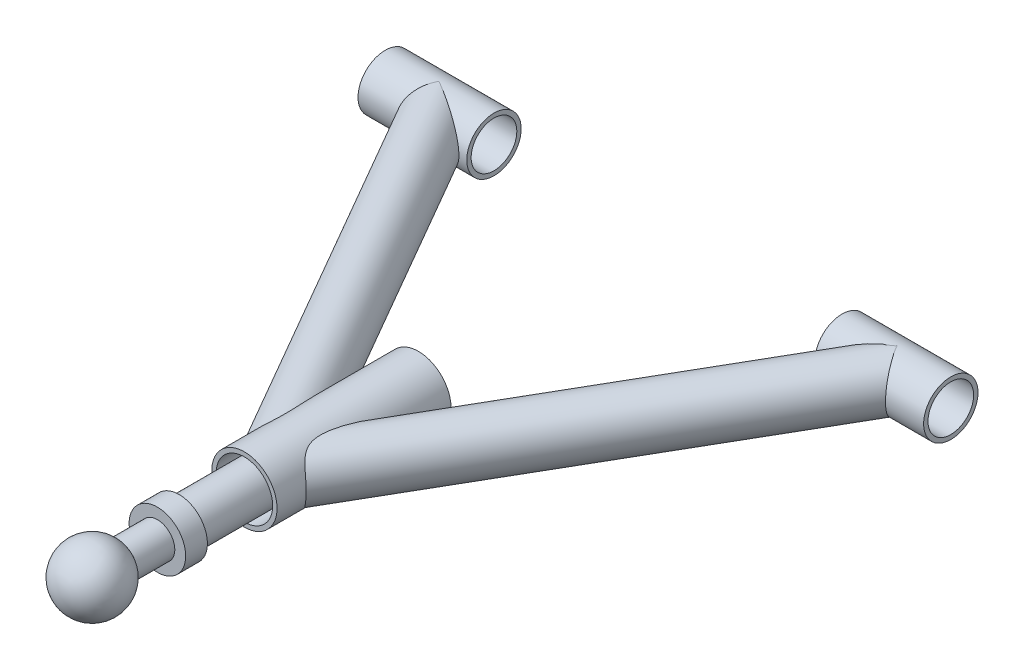
SolidWorks part; units mm, degrees
note: '?' marks a value the reader was unsure of.
ref_plane "前视基准面" through (0, 0, 0) normal (0, 0, 1) x (1, 0, 0)
ref_plane "上视基准面" through (0, 0, 0) normal (0, 1, 0) x (1, 0, 0)
ref_plane "右视基准面" through (0, 0, 0) normal (1, 0, 0) x (0, 0, -1)
sketch "草图1" plane through (0, 0, 0) normal (0, 0, 1) x (1, 0, 0)
  circle A0 centre (0, 0) radius 13
  circle A1 centre (0, 0) radius 15
  dimension "D1" = 30
  dimension "D2" = 2
extrude "凸台-拉伸1" add sketch "草图1" along normal blind 80
ref_axis "基准轴1" through (0, 13.75, 0) along (0, -1, 0)?
ref_plane "基准面1" through (0, 0, 0) normal (-0.5, 0, 0.866) x (0, -1, 0)
ref_plane "基准面2" through (0, 0, 0) normal (0.5, 0, 0.866) x (0, -1, 0)
sketch "草图3" plane through (0, 0, 0) normal (1, 0, 0) x (0, 0, -1)
  circle A0 centre (114.7344, 0) radius 12.5
  circle A1 centre (114.7344, 0) radius 10.5
  dimension "D2" = 25
  dimension "D1" = 2
extrude "凸台-拉伸3" add sketch "草图3" along normal blind 50 from offset 80 separate body
sketch "草图2" plane through (0, 0, 0) normal (-0.5, 0, 0.866) x (0, -1, 0)
  circle A0 centre (0, 33.8007) radius 12.5
  circle A1 centre (0, 33.8007) radius 10.5
  dimension "D1" = 25
  dimension "D2" = 2
extrude "凸台-拉伸2" add sketch "草图2" along normal up to next and the other way up to next
mirror "镜向14" about plane through (0, 0, 0) normal (1, 0, 0) of "凸台-拉伸1", "凸台-拉伸3", "凸台-拉伸2"
sketch "草图4" plane through (0, 0, 0) normal (0, 1, 0) x (1, 0, 0)
  line L0 (0, 0) -> (0, -165) construction
  line L1 (-8, -120) -> (-8, -137.3114)
  line L2 (-13, -110) -> (-10, -110)
  line L3 (-13, -110) -> (-13, -120)
  line L4 (-13, -120) -> (-8, -120)
  line L5 (-15, -80) -> (15, -80) construction
  line L6 (-10, -110) -> (-10, -74.7509)
  line L7 (-10, -74.7509) -> (0, -74.7509)
  line L8 (0, -74.7509) -> (0, -165)
  arc A0 (-8, -137.3114) -> (0, -165) centre (0, -150) ccw
  dimension "D1" = 30
  dimension "D8" = 70
  dimension "D2" = 8
  dimension "D3" = 10
  dimension "D4" = 3
  dimension "D5" = 30
  dimension "D6" = 10
revolve "旋转1" add sketch "草图4" angle 360 about L0
